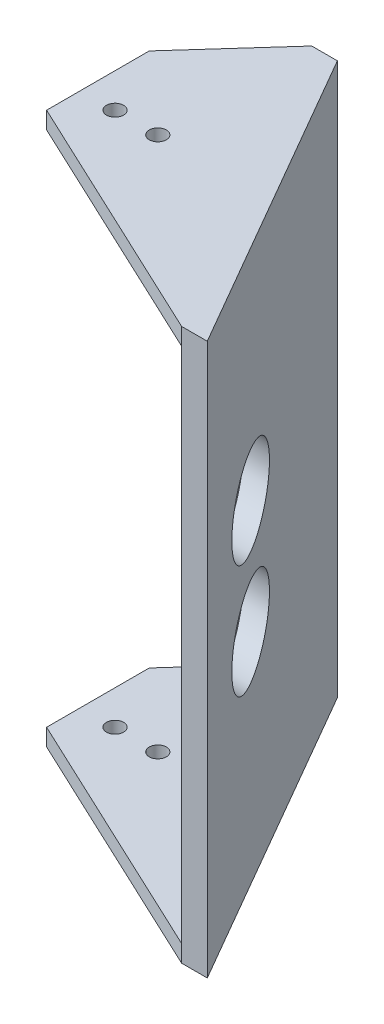
SolidWorks part; units mm, degrees
ref_plane "Front Plane" through (0, 0, 0) normal (0, 0, 1) x (1, 0, 0)
ref_plane "Top Plane" through (0, 0, 0) normal (0, 1, 0) x (1, 0, 0)
ref_plane "Right Plane" through (0, 0, 0) normal (1, 0, 0) x (0, 0, -1)
sketch "Sketch1" plane through (0, 0, 0) normal (0, 1, 0) x (1, 0, 0)
  line L0 (0, 0) -> (32.9956, 0)
  line L1 (32.9956, 0) -> (0, 57.15)
  line L2 (0, 57.15) -> (0, 0) construction
  line L3 (0, 28.575) -> (50000, 28.575) construction
  line L4 (0, 57.15) -> (-19.05, 57.15)
  line L5 (-19.05, 57.15) -> (-19.05, 0)
  line L6 (-19.05, 0) -> (0, 0)
  circle A0 centre (-12.7, 28.575) radius 1.5875
  circle A1 centre (-4.7625, 28.575) radius 1.5875
  point P6 (0, 28.575)
  point P11 (-3.1721, 28.575)
  dimension "D3" = 3.175
  dimension "D1" = 30
  dimension "D2" = 7.9375
  dimension "D4" = 6.35
  dimension "D6" = 19.05
extrude "Boss-Extrude1" add sketch "Sketch1" along normal blind 3.175
sketch "Sketch2" plane through (0, 0, 0) normal (0, -1, 0) x (1, 0, 0)
  line L0 (0, -57.15) -> (-4.7625, -57.15)
  line L1 (0, -57.15) -> (-19.05, -57.15) construction
  line L2 (-4.7625, -57.15) -> (28.2331, 0)
  line L3 (-19.05, 0) -> (32.9956, 0) construction
  line L4 (28.2331, 0) -> (32.9956, 0)
  line L9 (32.9956, 0) -> (-19.05, 0)
  line L10 (-19.05, 0) -> (-19.05, -57.15)
  line L11 (-19.05, -57.15) -> (0, -57.15)
  line L12 (0, -57.15) -> (32.9956, 0)
  line L16 (0, -57.15) -> (32.9956, 0)
  dimension "D1" = 4.7625
  dimension "D2" = 0
extrude "Boss-Extrude2" add sketch "Sketch2" along normal blind 96.012
sketch "Sketch3" plane through (0, -96.012, 0) normal (0, -1, 0) x (1, 0, 0)
  line L4 (32.9956, 0) -> (-19.05, 0)
  line L5 (0, -57.15) -> (32.9956, 0)
  line L6 (-19.05, -57.15) -> (0, -57.15)
  line L7 (-19.05, 0) -> (-19.05, -57.15)
  line L8 (32.9956, 0) -> (-19.05, 0)
  line L9 (0, -57.15) -> (32.9956, 0)
  line L10 (-19.05, -57.15) -> (0, -57.15)
  line L11 (-19.05, 0) -> (-19.05, -57.15)
  circle A0 centre (-12.7, -28.575) radius 1.5875 construction
  circle A1 centre (-4.7625, -28.575) radius 1.5875 construction
  circle A2 centre (-12.7, -28.575) radius 1.5875
  circle A3 centre (-4.7625, -28.575) radius 1.5875
  dimension "D1" = 0
extrude "Boss-Extrude3" add sketch "Sketch3" along normal blind 3.175
sketch "Sketch4" plane through (0, 0, 0) normal (0, -1, 0) x (1, 0, 0)
  line L0 (28.2331, 0) -> (-19.05, 0)
  line L1 (-19.05, 0) -> (-19.05, -22.225)
  line L2 (-19.05, -57.15) -> (-19.05, 0) construction
  line L3 (-19.05, -22.225) -> (15.4015, -22.225) construction
  line L4 (28.2331, 0) -> (-4.7625, -57.15) construction
  line L5 (15.4015, -22.225) -> (28.2331, 0) construction
  line L6 (-19.05, -22.225) -> (28.2331, 0)
  line L7 (-4.7625, -57.15) -> (-19.05, -41.275)
  line L8 (-19.05, -41.275) -> (-19.05, -57.15)
  line L9 (-19.05, -57.15) -> (-4.7625, -57.15)
  circle A0 centre (-12.7, -28.575) radius 1.5875 construction
  dimension "D1" = 6.35
  dimension "D2" = 15.875
extrude "Cut-Extrude1" cut sketch "Sketch4" against normal through all both and the other way through all
sketch "Sketch5" plane through (-19.05, 0, 0) normal (-1, 0, 0) x (0, 0, 1)
  line L0 (-19.05, -96.012) -> (-19.05, 0) construction
  line L4 (0, 0) -> (-57.15, 0)
  line L5 (-57.15, 0) -> (-57.15, -96.012)
  line L6 (-57.15, -96.012) -> (0, -96.012)
  line L7 (0, -96.012) -> (0, 0)
  line L8 (0, 0) -> (-57.15, 0) construction
  line L9 (-57.15, 0) -> (-57.15, -96.012) construction
  line L10 (-57.15, -96.012) -> (0, -96.012) construction
  line L11 (0, -96.012) -> (0, 0) construction
  circle A0 centre (-19.05, -58.547) radius 8.255
  circle A1 centre (-19.05, -37.465) radius 8.255
  point P10 (-19.05, -48.006)
  dimension "D5" = 16.51
  dimension "D2" = 19.05
  dimension "D3" = 21.082
  dimension "D4" = 10.541
  dimension "D1" = 0
extrude "Cut-Extrude2" cut sketch "Sketch5" against normal through all
